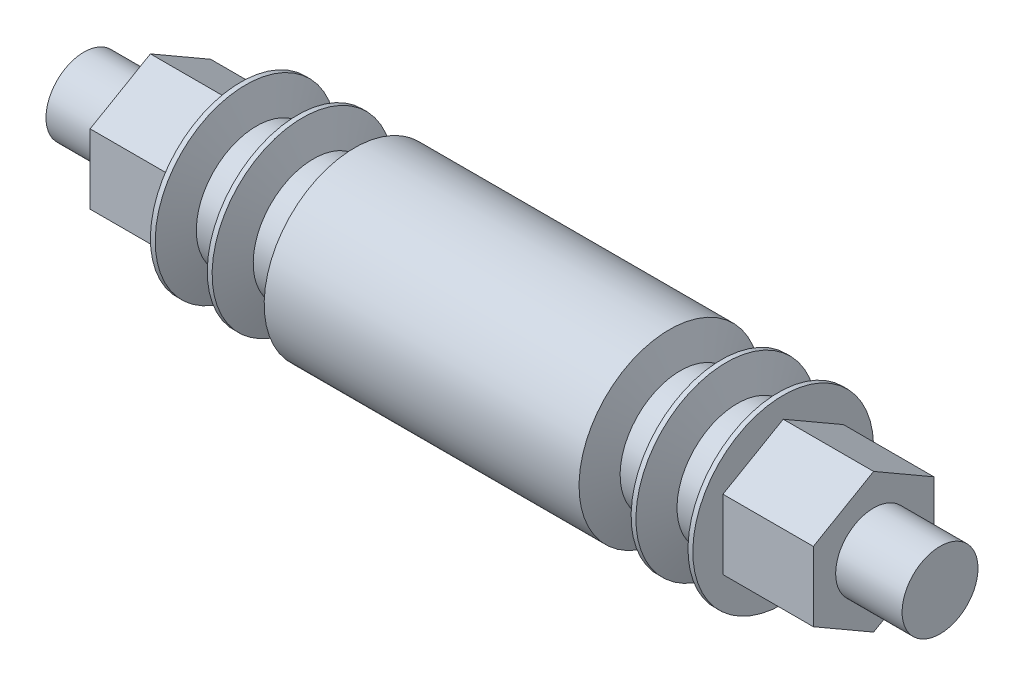
SolidWorks part; units mm, degrees
ref_plane "Front Plane" through (0, 0, 0) normal (0, 0, 1) x (1, 0, 0)
ref_plane "Top Plane" through (0, 0, 0) normal (0, 1, 0) x (1, 0, 0)
ref_plane "Right Plane" through (0, 0, 0) normal (1, 0, 0) x (0, 0, -1)
sketch "Sketch1" plane through (0, 0, 0) normal (0, 0, 1) x (1, 0, 0)
  line L0 (-38.1, 0) -> (38.1, 0) construction
  line L1 (-28.067, 9.525) -> (-26.9114, 6.35)
  line L2 (-26.9114, 6.35) -> (-23.7364, 6.35)
  line L3 (-23.7364, 6.35) -> (-22.5808, 9.525)
  line L4 (-22.5808, 9.525) -> (-22.0728, 9.525)
  line L5 (-22.0728, 9.525) -> (-20.9172, 6.35)
  line L6 (-20.9172, 6.35) -> (-17.7422, 6.35)
  line L7 (-17.7422, 6.35) -> (-16.5866, 9.525)
  line L8 (0, 0) -> (0, 25.6809) construction
  line L9 (-16.5866, 9.525) -> (0, 9.525)
  line L10 (-22.3268, 9.525) -> (-22.3268, 0) construction
  line L11 (-28.575, 9.525) -> (-28.575, 4.254)
  line L12 (-28.575, 4.254) -> (-38.1, 4.254)
  line L13 (-38.1, 4.254) -> (-38.1, 4)
  line L14 (-38.1, 0) -> (-28.575, 0)
  line L15 (-28.575, 0) -> (0, 0)
  line L16 (-28.067, 9.525) -> (-28.575, 9.525)
  line L17 (0, 0) -> (0, 9.525)
  line L18 (-38.1, 0) -> (-38.1, -4) construction
  line L19 (-28.575, 4.254) -> (-28.575, 0) construction
  line L20 (-45.1, 4) -> (-45.1, 0)
  line L21 (-45.1, 4) -> (-38.1, 4)
  line L22 (-45.1, 0) -> (-45.1, -4) construction
  line L23 (-38.1, 4) -> (-38.1, 0) construction
  line L24 (-38.1, 0) -> (-45.1, 0)
  point P1 (0, 3.4112)
  point P26 (0, 0)
  dimension "D2" = 3.175
  dimension "D3" = 3.175
  dimension "D4" = 70
  dimension "D5" = 0.508
  dimension "D6" = 3.175
  dimension "D7" = 3.175
  dimension "D8" = 0.508
  dimension "D9" = 76.2
  dimension "D10" = 0.254
  dimension "D11" = 9.525
  dimension "D12" = 8
  dimension "D13" = 7
  dimension "D14" = 9.525
revolve "Revolve1" add sketch "Sketch1" angle 360 about L0
sketch "Sketch4" plane through (-28.575, 0, 0) normal (-1, 0, 0) x (0, 0, 1)
  line L1 (0, 7.3323) -> (-6.35, 3.6662)
  line L2 (-6.35, 3.6662) -> (-6.35, -3.6662)
  line L3 (-6.35, -3.6662) -> (0, -7.3323)
  line L4 (0, -7.3323) -> (6.35, -3.6662)
  line L5 (6.35, -3.6662) -> (6.35, 3.6662)
  line L6 (6.35, 3.6662) -> (0, 7.3323)
  circle A0 centre (0, 0) radius 6.35 construction
  dimension "D1" = 12.7
extrude "Boss-Extrude4" add sketch "Sketch4" along normal up to surface (9.525 mm away) up to face at (-38.1, -4, 0)
mirror "Mirror1" about plane through (0, 0, 0) normal (1, 0, 0) of "Boss-Extrude4", "Revolve1"
